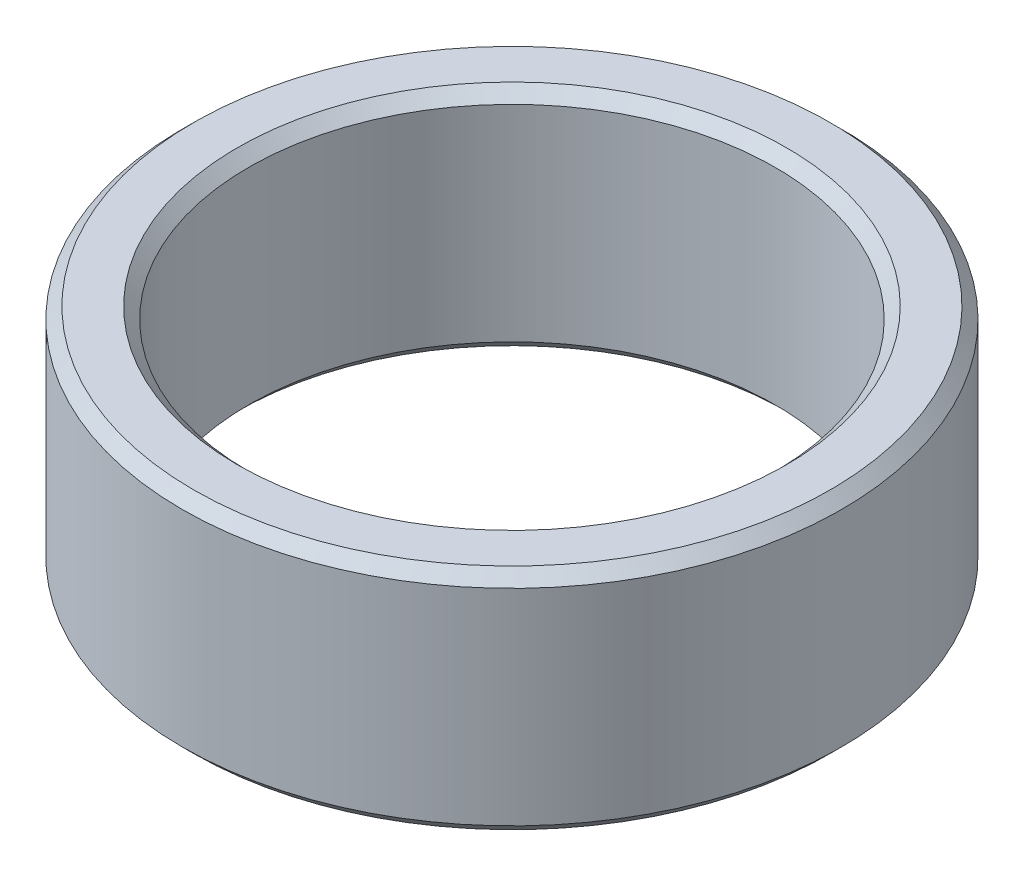
SolidWorks part; units mm, degrees
ref_plane "Front Plane" through (0, 0, 0) normal (0, 0, 1) x (1, 0, 0)
ref_plane "Top Plane" through (0, 0, 0) normal (0, 1, 0) x (1, 0, 0)
ref_plane "Right Plane" through (0, 0, 0) normal (1, 0, 0) x (0, 0, -1)
sketch "Sketch1" plane through (0, 0, 0) normal (0, 1, 0) x (1, 0, 0)
  circle A0 centre (0, 0) radius 50
  dimension "SLEEVE_OD" = 100
extrude "Boss-Extrude1" add sketch "Sketch1" along normal blind 34.6418
sketch "Sketch2" plane through (0, 0, 0) normal (0, 1, 0) x (1, 0, 0)
  circle A0 centre (0, 0) radius 39.9413
  dimension "BORE_D" = 79.8826
extrude "Cut-Extrude1" cut sketch "Sketch2" along normal through all
chamfer "Chamfer1" distance 1.7187 angle 45 4 edges at (0, 34.6418, 39.9413) (0, 0, 39.9413) (0, 0, 50) (0, 34.6418, 50)
